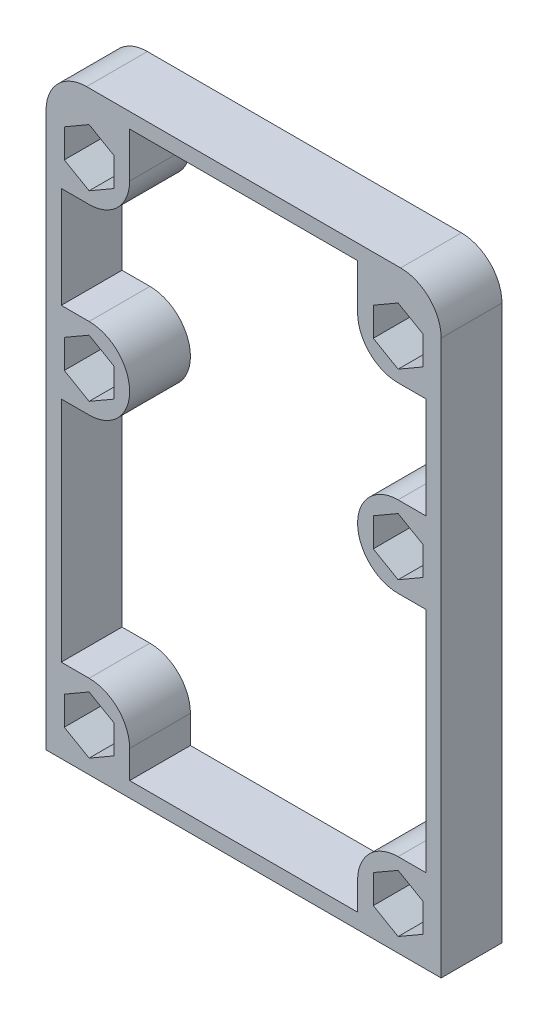
SolidWorks part; units mm, degrees
ref_plane "Front Plane" through (0, 0, 0) normal (0, 0, 1) x (1, 0, 0)
ref_plane "Top Plane" through (0, 0, 0) normal (0, 1, 0) x (1, 0, 0)
ref_plane "Right Plane" through (0, 0, 0) normal (1, 0, 0) x (0, 0, -1)
sketch "Sketch1" plane through (0, 0, 0) normal (0, 0, 1) x (1, 0, 0)
  line L0 (-19.5, 31.8137) -> (-19.5, -19.5)
  line L1 (-15.5, 39.2) -> (15.5, 39.2)
  line L2 (19.5, 35.2) -> (19.5, -19.5)
  line L3 (-19.5, -19.5) -> (19.5, -19.5)
  line L4 (-11.25, -18) -> (-11.25, -15.25)
  line L5 (-11.25, 33.25) -> (-11.25, 37.7)
  line L6 (15.25, 29.25) -> (18, 29.25)
  line L7 (0, -19.5) -> (0, 39.2) construction
  line L8 (-18, 31.8137) -> (-18, -18)
  line L9 (-18, -18) -> (18, -18)
  line L10 (18, 35.2) -> (18, -18)
  line L11 (-15.5, 37.7) -> (15.5, 37.7)
  line L12 (-18, 31.8137) -> (-18, 35.2)
  line L13 (11.25, 33.25) -> (11.25, 37.7)
  line L14 (18, 8.6) -> (19.5, 8.6) construction
  line L16 (-15.25, 29.25) -> (-18, 29.25)
  line L17 (-15.25, 19.25) -> (-18, 19.25)
  line L18 (-15.25, 11.25) -> (-18, 11.25)
  line L19 (-15.25, -11.25) -> (-18, -11.25)
  line L20 (15.25, 19.25) -> (18, 19.25)
  line L21 (15.25, 11.25) -> (18, 11.25)
  line L22 (15.25, -11.25) -> (18, -11.25)
  line L23 (11.25, -15.25) -> (11.25, -18)
  line L24 (-15.5, 39.2) -> (6.95, 39.2) construction
  line L25 (16.9, -15.25) -> (19.5, -15.25) construction
  line L26 (-19.5, 31.8137) -> (-19.5, 35.2)
  line L27 (15.25, -16.9) -> (15.25, -19.5) construction
  line L28 (15.25, 30.421) -> (17.7, 31.8355)
  line L29 (-15.25, 30.421) -> (-12.8, 31.8355)
  line L30 (-12.8, 31.8355) -> (-12.8, 34.6645)
  line L31 (-12.8, 34.6645) -> (-15.25, 36.079)
  line L32 (-15.25, 36.079) -> (-17.7, 34.6645)
  line L33 (-17.7, 34.6645) -> (-17.7, 31.8355)
  line L34 (-17.7, 31.8355) -> (-15.25, 30.421)
  line L35 (17.7, 31.8355) -> (17.7, 34.6645)
  line L36 (17.7, 34.6645) -> (15.25, 36.079)
  line L37 (15.25, 36.079) -> (12.8, 34.6645)
  line L38 (12.8, 34.6645) -> (12.8, 31.8355)
  line L39 (12.8, 31.8355) -> (15.25, 30.421)
  line L40 (-15.25, 12.421) -> (-12.8, 13.8355)
  line L41 (-12.8, 13.8355) -> (-12.8, 16.6645)
  line L42 (-12.8, 16.6645) -> (-15.25, 18.079)
  line L43 (-15.25, 18.079) -> (-17.7, 16.6645)
  line L44 (-17.7, 16.6645) -> (-17.7, 13.8355)
  line L45 (-17.7, 13.8355) -> (-15.25, 12.421)
  line L46 (15.25, 12.421) -> (17.7, 13.8355)
  line L47 (17.7, 13.8355) -> (17.7, 16.6645)
  line L48 (17.7, 16.6645) -> (15.25, 18.079)
  line L49 (15.25, 18.079) -> (12.8, 16.6645)
  line L50 (12.8, 16.6645) -> (12.8, 13.8355)
  line L51 (12.8, 13.8355) -> (15.25, 12.421)
  line L52 (-15.25, -18.079) -> (-12.8, -16.6645)
  line L53 (-12.8, -16.6645) -> (-12.8, -13.8355)
  line L54 (-12.8, -13.8355) -> (-15.25, -12.421)
  line L55 (-15.25, -12.421) -> (-17.7, -13.8355)
  line L56 (-17.7, -13.8355) -> (-17.7, -16.6645)
  line L57 (-17.7, -16.6645) -> (-15.25, -18.079)
  line L58 (15.25, -12.421) -> (12.8, -13.8355)
  line L59 (12.8, -13.8355) -> (12.8, -16.6645)
  line L60 (12.8, -16.6645) -> (15.25, -18.079)
  line L61 (15.25, -18.079) -> (17.7, -16.6645)
  line L62 (17.7, -16.6645) -> (17.7, -13.8355)
  line L63 (17.7, -13.8355) -> (15.25, -12.421)
  circle A0 centre (15.25, 33.25) radius 4
  circle A1 centre (15.25, 33.25) radius 1.65 construction
  circle A2 centre (-15.25, 33.25) radius 1.65 construction
  circle A3 centre (15.25, 33.25) radius 1.65
  circle A4 centre (-15.25, 33.25) radius 1.65
  circle A5 centre (15.25, -15.25) radius 1.65 construction
  circle A6 centre (15.25, 15.25) radius 1.65 construction
  circle A7 centre (15.25, -15.25) radius 1.65
  arc A8 (15.5, 37.7) -> (18, 35.2) centre (15.5, 35.2) cw
  arc A9 (-15.5, 37.7) -> (-18, 35.2) centre (-15.5, 35.2) ccw
  circle A10 centre (-15.25, 33.25) radius 4
  circle A11 centre (-15.25, 15.25) radius 4
  circle A12 centre (-15.25, -15.25) radius 4
  circle A13 centre (15.25, 15.25) radius 4
  circle A14 centre (15.25, -15.25) radius 4
  circle A15 centre (-15.25, 33.25) radius 2.45 construction
  circle A16 centre (15.25, 33.25) radius 2.45 construction
  circle A17 centre (-15.25, 15.25) radius 2.45 construction
  circle A18 centre (15.25, 15.25) radius 2.45 construction
  circle A19 centre (-15.25, -15.25) radius 2.45 construction
  circle A20 centre (15.25, -15.25) radius 2.45 construction
  circle A24 centre (15.25, 15.25) radius 1.65
  circle A25 centre (-15.25, 15.25) radius 1.65 construction
  circle A26 centre (-15.25, -15.25) radius 1.65 construction
  circle A27 centre (-15.25, 15.25) radius 1.65
  circle A28 centre (-15.25, -15.25) radius 1.65
  arc A29 (-15.5, 39.2) -> (-19.5, 35.2) centre (-15.5, 35.2) ccw construction
  arc A30 (-15.5, 39.2) -> (-19.5, 35.2) centre (-15.5, 35.2) ccw
  arc A31 (15.5, 39.2) -> (19.5, 35.2) centre (15.5, 35.2) cw
  dimension "D3" = 8
  dimension "D2" = 4.9
  dimension "D1" = 1.5
extrude "Base shape" add sketch "Sketch1" along normal blind 6 contours A31 L1 A30 L26 L0 L3 L2 A14 L9 A12 L8 A11 A10 A9 L11 A8 A0 L10 A13 | A12 L8 L9 L57 L56 L55 L54 L53 L52 | L8 A12 L9 L52 L57 | A11 L8 L45 L44 L43 L42 L41 L40 | L8 A11 | A11 L8 L18 | A11 L17 L8 | A10 A9 L12 L8 L34 L33 L32 L31 L30 L29 | A10 L8 L16 | A9 A10 L8 L12 | A10 L5 L11 A9 | A8 L11 L13 A0 | A8 A0 L10 L39 L38 L37 L36 L35 L28 | A0 A8 L10 | A0 L6 L10 | L10 A13 L51 L50 L49 L48 L47 L46 | A13 L10 L20 | L10 A13 | A13 L21 L10 | A12 L19 L8 | A12 L9 L4 | L9 A14 L10 L61 L60 | L10 A14 L9 L60 L59 L58 L63 L62 L61 | A14 L23 L9 | A14 L10 L22 region at (-19.4295, 33.5069, 0) region at (-11.5691, -17.3327, 0) region at (-11.6226, -16.6947, 0) region at (11.5691, -17.3327, 0) region at (-18.0094, -18.0094, 0) region at (-17.3327, -11.5691, 0) region at (11.6226, -16.6947, 0) region at (13.7292, -18.0976, 0) region at (17.3327, -11.5691, 0) region at (-17.3327, 11.5691, 0) region at (-18.5074, 15.25, 0) region at (-17.8953, 15.25, 0) region at (17.3327, 11.5691, 0) region at (-17.3327, 18.9309, 0) region at (16.6913, 11.6311, 0) region at (18.5074, 15.25, 0) region at (17.3327, 18.9309, 0) region at (-17.3327, 29.5691, 0) region at (-18.4973, 33.2967, 0) region at (-17.8953, 31.0795, 0) region at (17.3327, 29.5691, 0) region at (-13.0877, 36.8204, 0) region at (12.4956, 30.4956, 0) region at (18.4973, 33.2967, 0) region at (13.0877, 36.8204, 0)
